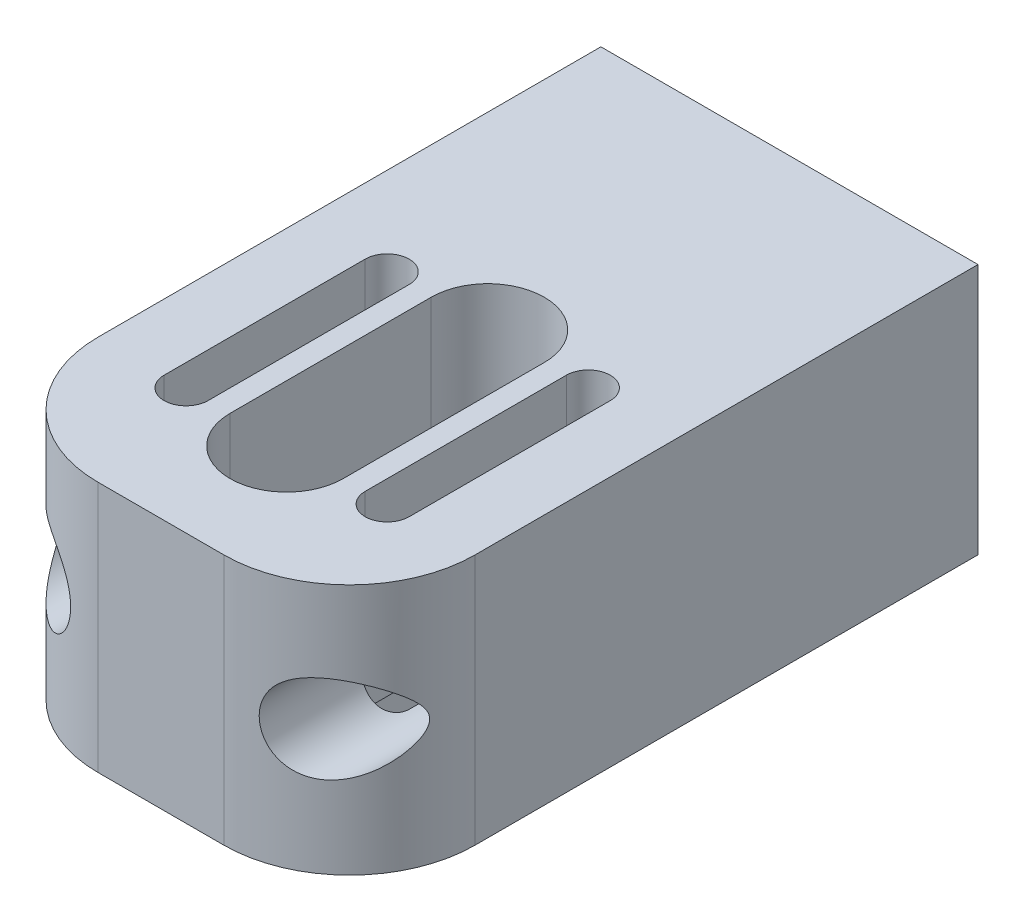
SolidWorks part; units mm, degrees
material "ABS"
ref_plane "Front Plane" through (0, 0, 0) normal (0, 0, 1) x (1, 0, 0)
ref_plane "Top Plane" through (0, 0, 0) normal (0, 1, 0) x (1, 0, 0)
ref_plane "Right Plane" through (0, 0, 0) normal (1, 0, 0) x (0, 0, -1)
sketch "Sketch1" plane through (0, 0, 0) normal (0, 0, 1) x (1, 0, 0)
  line L1 (-15.0008, -5.0578) -> (14.9992, -5.0578)
  line L2 (-15.0008, -5.0578) -> (-15.0008, 14.9422)
  line L3 (-15.0008, 14.9422) -> (14.9992, 14.9422)
  line L4 (14.9992, -5.0578) -> (14.9992, 14.9422)
  point P0 (0, 0)
  point P6 (0, 0)
  dimension "D1" = 20
  dimension "D3" = 30
extrude "Boss-Extrude1" add sketch "Sketch1" along normal blind 50
ref_plane "Plane1" through (-0.0008, 0, 0) normal (1, 0, 0) x (0, 0, -1)
sketch "Sketch3" plane through (0, 14.9422, 0) normal (0, 1, 0) x (1, 0, 0)
  line L1 (14.9992, -50) -> (-15.0008, -50) construction
  line L2 (-0.0009, -19.5) -> (-0.0009, -24) construction
  line L3 (-4.5008, -24) -> (-4.5002, -40)
  line L11 (-0.0007, -44.5) -> (-0.0006, -40) construction
  line L18 (4.4989, -40) -> (4.4989, -24)
  arc A6 (4.4989, -40) -> (-4.5002, -40) centre (-0.0006, -40) cw
  arc A7 (4.4989, -24) -> (-4.5008, -24) centre (-0.0009, -24) ccw
  dimension "D1" = 16
  dimension "D2" = 10
  dimension "D4" = 4.5
  dimension "D5" = 4.5
extrude "Cut-Extrude5" cut sketch "Sketch3" against normal through all
sketch "Sketch5" plane through (0, 14.9422, 0) normal (0, 1, 0) x (1, 0, 0)
  line L1 (-4.5002, -40) -> (-8.0008, -40) construction
  line L4 (-0.0008, -11) -> (-0.0008, 11) construction
  line L8 (-4.5008, -24) -> (-8.0008, -24) construction
  line L9 (-9.7511, -40) -> (-9.7511, -24)
  line L10 (-6.2505, -40) -> (-6.2505, -24)
  arc A8 (-6.2505, -40) -> (-9.7511, -40) centre (-8.0008, -40) cw
  arc A9 (-9.7511, -24) -> (-6.2505, -24) centre (-8.0008, -24) cw
  dimension "D1" = 8
extrude "Cut-Extrude2" cut sketch "Sketch5" against normal blind 20
sketch "Sketch6" plane through (0, -5.0578, 0) normal (0, -1, 0) x (1, 0, 0)
  line L0 (-9.7511, 40) -> (-6.2505, 24) construction
  line L1 (-6.2505, 40) -> (-9.7511, 24) construction
  line L8 (-11.0008, 43) -> (-5.0008, 43)
  line L9 (-11.0008, 43) -> (-11.0008, 21)
  line L10 (-11.0008, 21) -> (-5.0008, 21)
  line L11 (-5.0008, 43) -> (-5.0008, 21)
  line L12 (-11.0008, 43) -> (-5.0008, 21) construction
  line L13 (-11.0008, 21) -> (-5.0008, 43) construction
  point P9 (-8.0008, 32)
  dimension "D1" = 22
  dimension "D2" = 6
extrude "Cut-Extrude3" cut sketch "Sketch6" against normal blind 5
sketch "Sketch7" plane through (0, 0, 50) normal (0, 0, 1) x (1, 0, 0)
  line L0 (-15.0008, 4.9422) -> (14.9992, 4.9422) construction
  line L1 (-15.0008, 14.9422) -> (-15.0008, -5.0578) construction
  line L2 (14.9992, -5.0578) -> (14.9992, 14.9422) construction
  circle A0 centre (-11.0008, 4.9422) radius 1.75
  dimension "D1" = 3.5
  dimension "D3" = 4
extrude "Cut-Extrude4" cut sketch "Sketch7" against normal through all
hole_wizard "CBORE for M3 Hex Socket Head Cap Screw1" positions "Sketch9" profile "Sketch8" counterbore size "M3" standard "ISO" end condition through all
sketch "Sketch9" plane through (0, 0, 50) normal (0, 0, 1) x (1, 0, 0)
  point P0 (-11.0008, 4.9422)
sketch "Sketch8" plane through (-11.0008, 4.9422, 50) normal (1, 0, 0) x (0, -1, 0)
  line L0 (0, 0) -> (0, 50)
  line L1 (0, 50) -> (1.7, 50)
  line L3 (1.7, 50) -> (1.7, 38.4)
  line L4 (1.7, 38.4) -> (3.5, 38.4)
  line L5 (3.5, 38.4) -> (3.5, 0)
  line L7 (3.5, 0) -> (0, 0)
  line L11 (0, -6.35) -> (0, 107.95) construction
  dimension "Thru Hole Dia." = 3.4
  dimension "Thru Hole Depth" = 50
  dimension "C'Bore Dia." = 7
  dimension "C'Bore Depth" = 38.4
fillet "Fillet1" radius 10 2 edges at (-15.0008, 4.9422, 50) (14.9992, 4.9422, 50)
mirror "Mirror1" about plane through (-0.0008, 0, 0) normal (1, 0, 0) of "Cut-Extrude4", "Cut-Extrude2", "Cut-Extrude3", "CBORE for M3 Hex Socket Head Cap Screw1"
